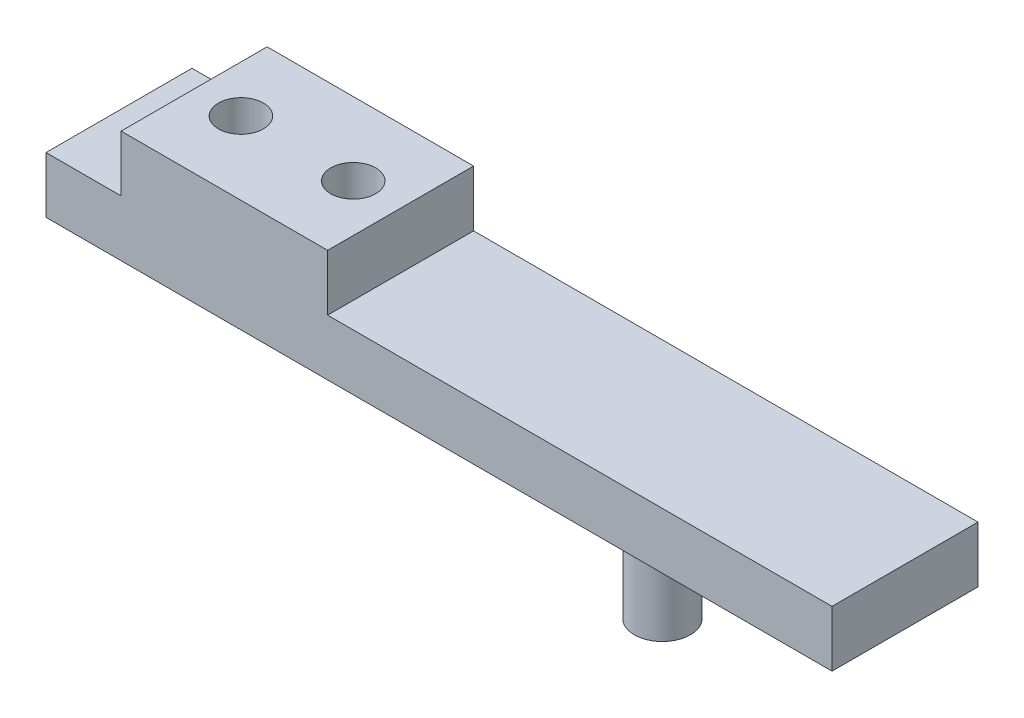
SolidWorks part; units mm, degrees
material "6061-T6 (SS)"
ref_plane "Front Plane" through (0, 0, 0) normal (0, 0, 1) x (1, 0, 0)
ref_plane "Top Plane" through (0, 0, 0) normal (0, 1, 0) x (1, 0, 0)
ref_plane "Right Plane" through (0, 0, 0) normal (1, 0, 0) x (0, 0, -1)
sketch "Sketch1" plane through (0, 0, 0) normal (0, 1, 0) x (1, 0, 0)
  line L1 (-35, 6.5) -> (35, 6.5)
  line L2 (-35, 6.5) -> (-35, -6.5)
  line L3 (-35, -6.5) -> (35, -6.5)
  line L4 (35, 6.5) -> (35, -6.5)
  line L5 (-35, 6.5) -> (35, -6.5) construction
  line L6 (-35, -6.5) -> (35, 6.5) construction
  point P0 (0, 0)
  dimension "D1" = 13
  dimension "D2" = 70
extrude "Boss-Extrude1" add sketch "Sketch1" along normal blind 5
sketch "Sketch2" plane through (0, 5, 0) normal (0, 1, 0) x (1, 0, 0)
  line L6 (-41.2697, 0) -> (45.9035, 0) construction
  line L7 (35, 6.5) -> (-35, 6.5) construction
  line L8 (-28.3096, 6.5) -> (-9.9192, 6.5)
  line L9 (-28.3096, 6.5) -> (-28.3096, -6.5)
  line L10 (-28.3096, -6.5) -> (-9.9192, -6.5)
  line L11 (-9.9192, 6.5) -> (-9.9192, -6.5)
  line L12 (-35, -6.5) -> (35, -6.5) construction
  circle A0 centre (-24.1413, 0) radius 2
  circle A1 centre (-14.1413, 0) radius 2
  dimension "D1" = 4
  dimension "D2" = 10
extrude "Cut-Extrude1" cut sketch "Sketch2" against normal through all contours L6 A0 | A0 L6 | L6 A1 | A1 L6 region at (-24.1413, 5, -0.8488) region at (-24.1413, 5, 0.8488) region at (-14.1413, 5, -0.8488) region at (-14.1413, 5, 0.8488)
extrude "Boss-Extrude3" add sketch "Sketch2<3>" along normal blind 5
sketch "Sketch2<3>" plane through (0, 5, 0) normal (0, 1, 0) x (1, 0, 0) same geometry as "Sketch2"
sketch "Sketch3" plane through (0, 0, 0) normal (0, -1, 0) x (-1, 0, 0)
  circle A1 centre (-13.3945, 0) radius 2.5
  dimension "D1" = 5
extrude "Boss-Extrude4" add sketch "Sketch3" along normal blind 10
